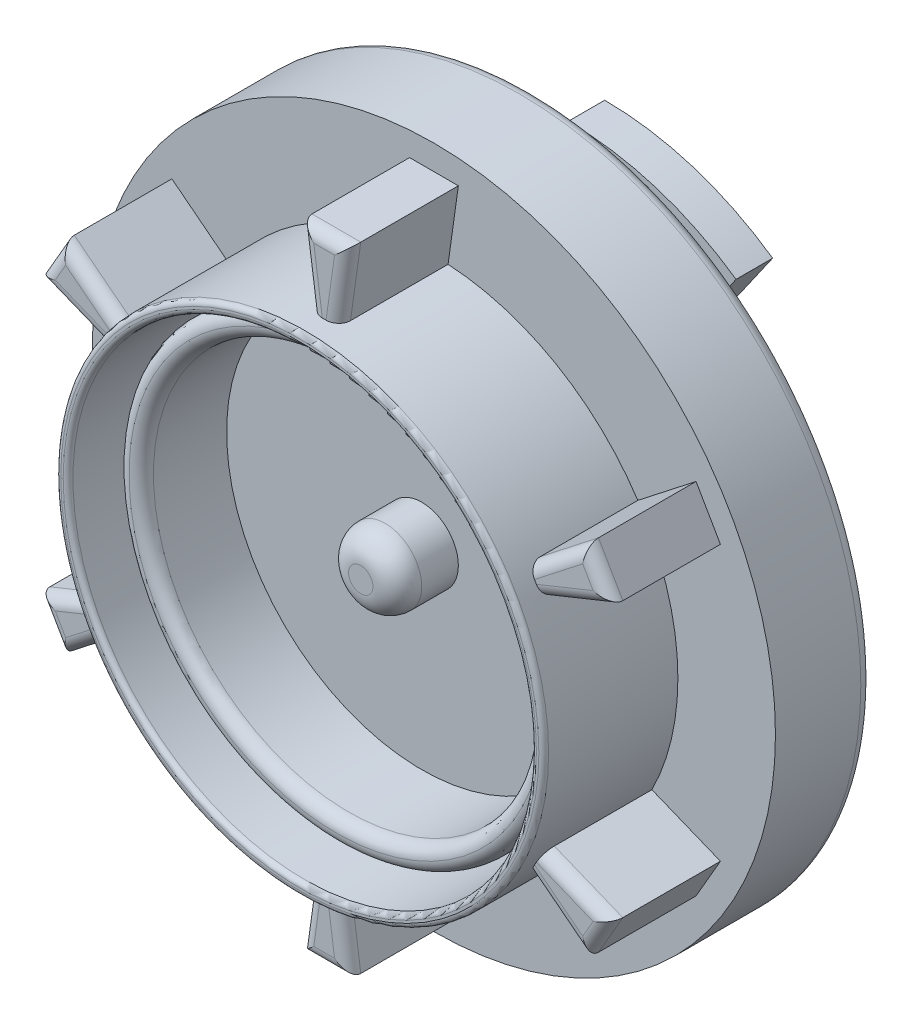
SolidWorks part; units mm, degrees
ref_plane "Front Plane" through (0, 0, 0) normal (0, 0, 1) x (1, 0, 0)
ref_plane "Top Plane" through (0, 0, 0) normal (0, 1, 0) x (1, 0, 0)
ref_plane "Right Plane" through (0, 0, 0) normal (1, 0, 0) x (0, 0, -1)
sketch "Sketch1" plane through (0, 0, 0) normal (0, 0, 1) x (1, 0, 0)
  circle A0 centre (0, 0) radius 25.4
  dimension "D1" = 50.8
extrude "Boss-Extrude1" add sketch "Sketch1" along normal blind 13.97
sketch "Sketch3" plane through (0, 0, 0) normal (0, 0, -1) x (-1, 0, 0)
  circle A0 centre (0, 0) radius 35.56
  dimension "D1" = 71.12
extrude "Boss-Extrude2" add sketch "Sketch3" along normal blind 10.16
sketch "Sketch4" plane through (0, 0, -10.16) normal (0, 0, -1) x (-1, 0, 0)
  circle A0 centre (0, 0) radius 17.78
  dimension "D1" = 35.56
extrude "Cut-Extrude2" cut sketch "Sketch4" against normal blind 10.16
sketch "Sketch5" plane through (0, 0, -10.16) normal (0, 0, -1) x (-1, 0, 0)
  line L0 (0, 36.6763) -> (0, -38.6732) construction
  line L1 (0, 0) -> (16.1177, -25.8699) construction
  line L2 (0, 24.13) -> (0, 33.02)
  line L3 (12.7598, -20.4803) -> (16.1177, -25.8699)
  arc A0 (0, 33.02) -> (19.765, 26.4512) centre (0, 0) cw
  circle A1 centre (0, 0) radius 35.56 construction
  arc A2 (19.765, 26.4512) -> (21.6061, 23.1161) centre (16.9977, 22.7478) cw
  arc A3 (21.6061, 23.1161) -> (22.86, 20.1606) centre (26.67, 23.5207) ccw
  arc A4 (22.86, 20.1606) -> (16.1177, -25.8699) centre (0, 0) cw
  arc A5 (0, -30.48) -> (16.1177, -25.8699) centre (0, 0) ccw construction
  arc A6 (12.7598, -20.4803) -> (0, 24.13) centre (0, 0) ccw
  circle A7 centre (0, 0) radius 35.56 construction
  dimension "D1" = 20.828
  dimension "D2" = 33.02
  dimension "D3" = 22.86
  dimension "D4" = 30.48
  dimension "D5" = 16.764
  dimension "D6" = 24.13
extrude "Cut-Extrude3" cut sketch "Sketch5" against normal blind 7.62
ref_plane "Plane1" through (0, 0, -7.62) normal (0, 0, -1) x (-1, 0, 0)
sketch "Sketch7" plane through (0, 0, -7.62) normal (0, 0, -1) x (-1, 0, 0)
  line L0 (0, 0) -> (16.1177, -25.8699) construction
  line L1 (17.4608, -28.0257) -> (16.1177, -25.8699)
  arc A0 (19.765, 26.4512) -> (17.4608, -28.0257) centre (0, 0) cw
  circle A1 centre (0, 0) radius 35.56 construction
  arc A2 (16.1177, -25.8699) -> (22.86, 20.1606) centre (0, 0) ccw
  arc A3 (16.1177, -25.8699) -> (22.86, 20.1606) centre (0, 0) ccw construction
  arc A4 (22.86, 20.1606) -> (21.6061, 23.1161) centre (26.67, 23.5207) cw
  arc A5 (21.6061, 23.1161) -> (19.765, 26.4512) centre (16.9977, 22.7478) ccw
extrude "Cut-Extrude4" cut sketch "Sketch7" against normal blind 5.08
sketch "Sketch8" plane through (0, 0, -10.16) normal (0, 0, -1) x (-1, 0, 0)
  line L0 (0, 0) -> (0, -41.8815) construction
  line L1 (0, -27.94) -> (0, -24.13)
  line L2 (12.7598, -20.4803) -> (16.1177, -25.8699) construction
  line L3 (12.7598, -20.4803) -> (14.7745, -23.7141)
  arc A0 (0, -27.94) -> (14.7745, -23.7141) centre (0, 0) ccw
  circle A2 centre (0, 0) radius 35.56 construction
  arc A3 (0, -24.13) -> (12.7598, -20.4803) centre (0, 0) ccw
  dimension "D1" = 24.13
  dimension "D2" = 3.81
extrude "Boss-Extrude3" add sketch "Sketch8" along normal blind 3.81
sketch "Sketch9" plane through (0, 0, -13.97) normal (0, 0, -1) x (-1, 0, 0)
  line L0 (0, -24.13) -> (0, -30.48)
  line L1 (0, 0) -> (14.7745, -23.7141) construction
  line L2 (12.7598, -20.4803) -> (16.1177, -25.8699)
  arc A0 (0, -24.13) -> (12.7598, -20.4803) centre (0, 0) ccw
  arc A1 (0, -24.13) -> (12.7598, -20.4803) centre (0, 0) ccw construction
  arc A2 (0, -30.48) -> (16.1177, -25.8699) centre (0, 0) ccw
  dimension "D1" = 6.35
extrude "Boss-Extrude4" add sketch "Sketch9" along normal blind 3.81
fillet "Fillet1" radius 1.27 1 edges at (-35.56, 0, -10.16)
sketch "Sketch10" plane through (0, 0, -10.16) normal (0, 0, -1) x (-1, 0, 0)
  line L0 (0, 33.02) -> (0, 24.13) construction
  line L3 (0, 0) -> (-16.002, 22.9037) construction
  line L4 (-13.8199, 19.7805) -> (-16.002, 22.9037)
  line L5 (0, 27.94) -> (0, 24.13)
  arc A0 (0, 24.13) -> (-13.8199, 19.7805) centre (0, 0) ccw
  arc A1 (0, 27.94) -> (-16.002, 22.9037) centre (0, 0) ccw
  circle A2 centre (0, 0) radius 35.56 construction
  dimension "D2" = 16.002
  dimension "D1" = 3.81
extrude "Boss-Extrude5" add sketch "Sketch10" along normal blind 3.81
sketch "Sketch11" plane through (0, 0, -13.97) normal (0, 0, -1) x (-1, 0, 0)
  line L1 (-13.8199, 19.7805) -> (-17.4865, 25.0285)
  line L2 (0, 24.13) -> (0, 30.5321)
  line L3 (-16.002, 22.9037) -> (-13.8199, 19.7805) construction
  arc A0 (-13.8199, 19.7805) -> (0, 24.13) centre (0, 0) cw
  arc A1 (0, 24.13) -> (-13.8199, 19.7805) centre (0, 0) ccw construction
  arc A2 (-17.4865, 25.0285) -> (0, 30.5321) centre (0, 0) cw
  circle A3 centre (0, 0) radius 34.29 construction
  dimension "D2" = 6.4021
extrude "Boss-Extrude6" add sketch "Sketch11" along normal blind 3.81
sketch "Sketch12" plane through (0, 0, -10.16) normal (0, 0, -1) x (-1, 0, 0)
  circle A0 centre (0, 0) radius 15.494
  circle A1 centre (0, 0) radius 19.685
  dimension "D1" = 30.988
  dimension "D2" = 39.37
extrude "Cut-Extrude5" cut sketch "Sketch12" against normal blind 5.08
sketch "Sketch13" plane through (0, 0, -10.16) normal (0, 0, -1) x (-1, 0, 0)
  line L0 (-16.002, 22.9037) -> (-13.8199, 19.7805)
  line L1 (0, -30.48) -> (0, -24.13)
  arc A0 (0, -30.48) -> (-19.5746, -23.3638) centre (0, 0) cw
  circle A1 centre (0, 0) radius 34.29 construction
  arc A2 (-19.5746, -23.3638) -> (-21.5114, -19.6967) centre (-16.0504, -19.1574) cw
  arc A3 (-21.5114, -19.6967) -> (-22.86, -16.0644) centre (-29.0945, -20.4456) ccw
  arc A4 (-22.86, -16.0644) -> (-16.002, 22.9037) centre (0, 0) cw
  circle A5 centre (0, 0) radius 35.56 construction
  arc A6 (0, -24.13) -> (-13.8199, 19.7805) centre (0, 0) cw
  dimension "D1" = 20.828
  dimension "D2" = 22.86
extrude "Cut-Extrude6" cut sketch "Sketch13" against normal blind 7.62
sketch "Sketch15" plane through (0, 0, -7.62) normal (0, 0, -1) x (-1, 0, 0)
  line L0 (-17.4865, 25.0285) -> (-13.8199, 19.7805) construction
  line L1 (-17.4567, 24.9859) -> (-16.002, 22.9037)
  arc A0 (-19.5746, -23.3638) -> (-17.4567, 24.9859) centre (0, 0) cw
  arc A1 (-19.5746, -23.3638) -> (-21.5114, -19.6967) centre (-16.0504, -19.1574) cw
  arc A2 (-21.5114, -19.6967) -> (-22.86, -16.0644) centre (-29.0945, -20.4456) ccw
  arc A3 (-22.86, -16.0644) -> (-16.002, 22.9037) centre (0, 0) cw
extrude "Cut-Extrude7" cut sketch "Sketch15" against normal blind 5.08 contours A3 L1 A0 A1 A2
sketch "Sketch16" plane through (0, 0, 0) normal (0, 0, 1) x (1, 0, 0)
  circle A0 centre (0, 0) radius 35.56
  dimension "D1" = 71.12
sketch "Sketch17" plane through (0, 0, 13.97) normal (0, 0, 1) x (1, 0, 0)
  circle A0 centre (0, 0) radius 24.13
  circle A2 centre (0, 0) radius 22.86
  dimension "D1" = 48.26
  dimension "D2" = 45.72
extrude "Cut-Extrude9" cut sketch "Sketch17" against normal blind 13.97
sketch "Sketch18" plane through (0, 0, 13.97) normal (0, 0, 1) x (1, 0, 0)
  circle A0 centre (0, 0) radius 20.32
  circle A1 centre (0, 0) radius 19.05
  dimension "D1" = 40.64
  dimension "D2" = 38.1
extrude "Cut-Extrude10" cut sketch "Sketch18" against normal blind 12.7
sketch "Sketch19" plane through (0, 0, 13.97) normal (0, 0, 1) x (1, 0, 0)
  circle A0 centre (0, 0) radius 19.05
  circle A1 centre (0, 0) radius 3.81
  dimension "D1" = 38.1
  dimension "D2" = 7.62
extrude "Cut-Extrude11" cut sketch "Sketch19" against normal blind 12.7
sketch "Sketch20" plane through (0, 0, 13.97) normal (0, 0, 1) x (1, 0, 0)
  circle A0 centre (0, 0) radius 3.81
  dimension "D1" = 7.62
extrude "Cut-Extrude12" cut sketch "Sketch20" against normal blind 6.35
fillet "Fillet3" radius 2.54 1 edges at (3.81, 0, 7.62)
fillet "Fillet5" radius 0.508 2 edges at (24.13, 0, 13.97) (25.4, 0, 13.97)
sketch "Sketch21" plane through (0, 0, 13.97) normal (0, 0, 1) x (1, 0, 0)
  circle A0 centre (0, 0) radius 20.32
  circle A1 centre (0, 0) radius 22.86
  dimension "D1" = 40.64
  dimension "D2" = 45.72
extrude "Cut-Extrude13" cut sketch "Sketch21" against normal blind 3.81
fillet "Fillet6" radius 1.27 2 edges at (22.86, 0, 10.16) (20.32, 0, 10.16)
sketch "Sketch22" plane through (0, 0, 0) normal (0, 0, 1) x (1, 0, 0)
  line L0 (-1.4691, 25.3575) -> (-2.54, 32.9775)
  line L1 (2.54, 32.9775) -> (1.4691, 25.3575)
  line L2 (0, 0) -> (0, 36.1761) construction
  line L3 (-2.54, 32.9775) -> (2.54, 32.9775)
  line L4 (21.2257, 13.951) -> (27.2893, 18.6884)
  line L5 (27.2893, 18.6884) -> (29.8293, 14.289)
  line L6 (29.8293, 14.289) -> (22.6948, 11.4065)
  line L7 (22.6948, -11.4065) -> (29.8293, -14.289)
  line L8 (29.8293, -14.289) -> (27.2893, -18.6884)
  line L9 (27.2893, -18.6884) -> (21.2257, -13.951)
  line L10 (1.4691, -25.3575) -> (2.54, -32.9775)
  line L11 (2.54, -32.9775) -> (-2.54, -32.9775)
  line L12 (-2.54, -32.9775) -> (-1.4691, -25.3575)
  line L13 (-21.2257, -13.951) -> (-27.2893, -18.6884)
  line L14 (-27.2893, -18.6884) -> (-29.8293, -14.289)
  line L15 (-29.8293, -14.289) -> (-22.6948, -11.4065)
  line L16 (-22.6948, 11.4065) -> (-29.8293, 14.289)
  line L17 (-29.8293, 14.289) -> (-27.2893, 18.6884)
  line L18 (-27.2893, 18.6884) -> (-21.2257, 13.951)
  arc A0 (-1.4691, 25.3575) -> (1.4691, 25.3575) centre (0, 0) cw
  circle A1 centre (0, 0) radius 25.4 construction
  arc A5 (21.2257, 13.951) -> (22.6948, 11.4065) centre (0, 0) cw
  arc A6 (22.6948, -11.4065) -> (21.2257, -13.951) centre (0, 0) cw
  arc A7 (1.4691, -25.3575) -> (-1.4691, -25.3575) centre (0, 0) cw
  arc A8 (-21.2257, -13.951) -> (-22.6948, -11.4065) centre (0, 0) cw
  arc A9 (-22.6948, 11.4065) -> (-21.2257, 13.951) centre (0, 0) cw
  point P32 (0, 0)
  dimension "D1" = 8
  dimension "D2" = 8
  dimension "D3" = 5.08
  dimension "D4" = 2.54
  dimension "D5" = 7.62
  dimension "D6" = 6
extrude "Boss-Extrude8" add sketch "Sketch22" along normal blind 11.43
fillet "Fillet7" radius 1.27 18 edges at (-26.262, -12.8478, 11.43) (-24.2575, -16.3197, 11.43) (-2.0045, -29.1675, 11.43) (2.0045, -29.1675, 11.43) (26.262, -12.8478, 11.43) (24.2575, -16.3197, 11.43) (26.262, 12.8478, 11.43) (24.2575, 16.3197, 11.43) (2.0045, 29.1675, 11.43) (-2.0045, 29.1675, 11.43) (-26.262, 12.8478, 11.43) (-24.2575, 16.3197, 11.43) (-28.5593, 16.4887, 11.43) (-28.5593, -16.4887, 11.43) (0, -32.9775, 11.43) (28.5593, -16.4887, 11.43) (28.5593, 16.4887, 11.43) (0, 32.9775, 11.43)
